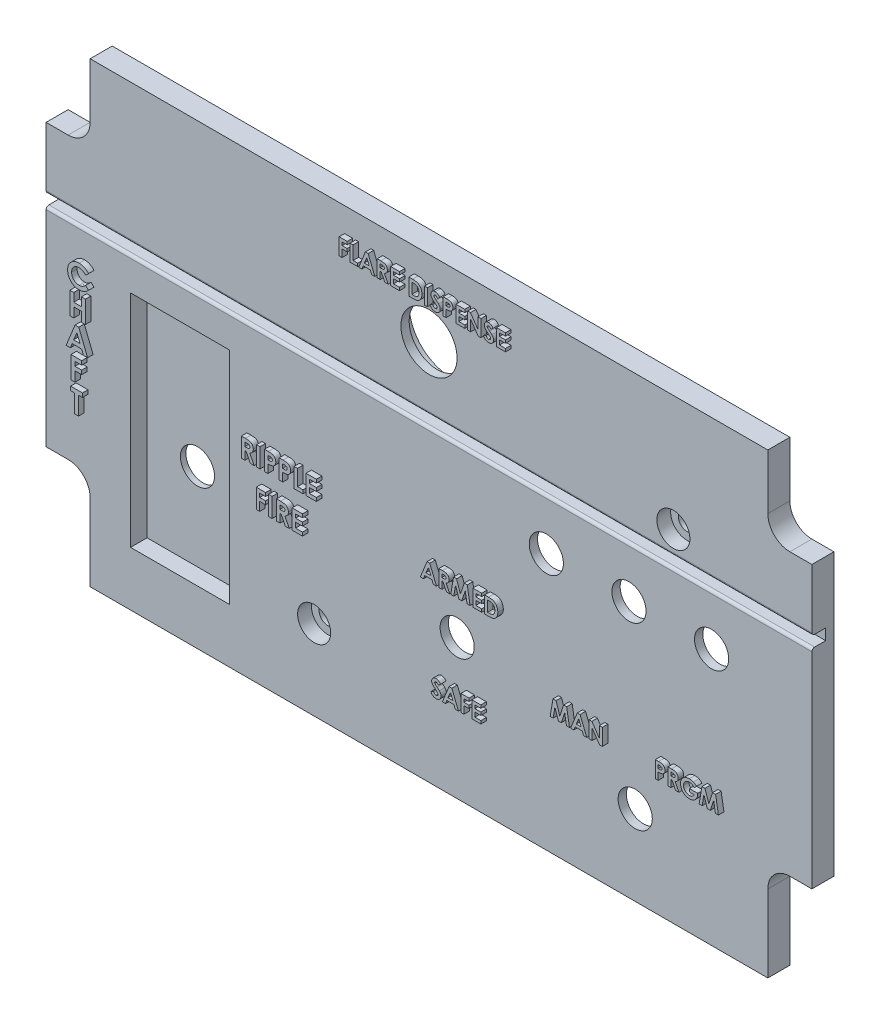
SolidWorks part; units mm, degrees
ref_plane "Front Plane" through (0, 0, 0) normal (0, 0, 1) x (1, 0, 0)
ref_plane "Top Plane" through (0, 0, 0) normal (0, 1, 0) x (1, 0, 0)
ref_plane "Right Plane" through (0, 0, 0) normal (1, 0, 0) x (0, 0, -1)
sketch "Sketch1" plane through (0, 0, 0) normal (0, 0, 1) x (1, 0, 0)
  line L1 (8, 6.6454) -> (131, 6.6454)
  line L2 (0, 24.6454) -> (0, 75.6454)
  line L3 (8, 89.6454) -> (131, 89.6454)
  line L4 (139, 24.6454) -> (139, 75.6454)
  line L13 (8, 89.6454) -> (8, 79.6454)
  line L14 (4, 75.6454) -> (0, 75.6454)
  line L15 (8, 6.6454) -> (8, 20.6454)
  line L16 (4, 24.6454) -> (0, 24.6454)
  line L17 (131, 89.6454) -> (131, 79.6454)
  line L18 (135, 75.6454) -> (139, 75.6454)
  line L19 (131, 6.6454) -> (131, 20.6454)
  line L20 (135, 24.6454) -> (139, 24.6454)
  line L23 (0, 0) -> (0, 87.0008) construction
  arc A8 (8, 20.6454) -> (4, 24.6454) centre (4, 20.6454) ccw
  arc A9 (8, 79.6454) -> (4, 75.6454) centre (4, 79.6454) cw
  arc A11 (131, 20.6454) -> (135, 24.6454) centre (135, 20.6454) cw
  arc A12 (131, 79.6454) -> (135, 75.6454) centre (135, 79.6454) ccw
  circle A14 centre (48.6544, 21.1904) radius 1.6 construction
  circle A15 centre (48.6544, 21.1904) radius 1.6
  circle A16 centre (90.8006, 53.2423) radius 3.1 construction
  circle A17 centre (105.8006, 53.2423) radius 3.1 construction
  circle A18 centre (120.8006, 53.2423) radius 3.1 construction
  circle A19 centre (90.8006, 53.2423) radius 3.1
  circle A35 centre (105.8006, 53.2423) radius 3.1
  circle A37 centre (120.8006, 53.2423) radius 3.1
  circle A47 centre (69.5, 75.8772) radius 5.1 construction
  circle A48 centre (106.9326, 21.1904) radius 3.1 construction
  circle A49 centre (74.6156, 32.0065) radius 3.1 construction
  circle A50 centre (24.475, 32.312) radius 3.1 construction
  circle A51 centre (69.5, 75.8772) radius 5.1
  circle A52 centre (106.9326, 21.1904) radius 3.1
  circle A53 centre (74.6156, 32.0065) radius 3.1
  circle A54 centre (24.475, 32.312) radius 3.1
  circle A55 centre (113.8581, 68.5981) radius 1.6 construction
  circle A56 centre (113.8581, 68.5981) radius 1.6
  point P21 (131, 24.6454)
  point P25 (8, 75.6454)
  point P40 (131, 75.6454)
  dimension "D3" = 18
  dimension "D4" = 14
  dimension "D5" = 8
  dimension "D7" = 83
  dimension "D11" = 8
  dimension "D16" = 139
  dimension "D22" = 8
  dimension "D9" = 8
extrude "Boss-Extrude1" add sketch "Sketch1" along normal blind 4
sketch "Sketch4" plane through (0, 0, 4) normal (0, 0, 1) x (1, 0, 0)
  line L0 (8, 54.5551) -> (8, 14.5758) construction
  line L1 (8, 89.6454) -> (8, 79.6454) construction
  line L2 (-3.2263, 38.4147) -> (14.9404, 38.4147) construction
  line L3 (-3.2263, 33.4147) -> (15.4271, 33.4147) construction
  line L4 (-2.9665, 53.4147) -> (15.2002, 53.4147) construction
  line L5 (-2.9665, 48.4147) -> (15.2002, 48.4147) construction
  line L6 (-2.9665, 43.4147) -> (15.2002, 43.4147) construction
  line L7 (5, 54.5551) -> (5, 14.5758) construction
  text T0 "<b>C</b>" font "Century Gothic" height 4
  text T1 "<b>T</b>" font "Century Gothic" height 4
  text T2 "<b>RIPPLE</b>\r\n<b>  FIRE</b>" font "Century Gothic" height 3.5
  text T5 "<b>F</b>" font "Century Gothic" height 4
  text T7 "<b>FLARE DISPENSE</b>" font "Century Gothic" height 3
  text T9 "<b>H</b>" font "Century Gothic" height 4
  text T10 "<b>A</b>" font "Century Gothic" height 4
  text T11 "<b>ARMED</b>" font "Century Gothic" height 3
  text T12 "<b>SAFE</b>" font "Century Gothic" height 3
  text T13 "<b>MAN</b>" font "Century Gothic" height 3
  text T15 "<b>PRGM</b>" font "Century Gothic" height 3
  dimension "D1" = 3
  dimension "D2" = 5
  dimension "D3" = 5
  dimension "D4" = 5
  dimension "D5" = 5
extrude "Textos" add sketch "Sketch4" along normal blind 1
sketch "Sketch8" plane through (0, 0, 4) normal (0, 0, 1) x (1, 0, 0)
  line L2 (33.3358, 56.5063) -> (15.3354, 56.5063)
  line L3 (33.3358, 56.5063) -> (33.3358, 16.5063)
  line L4 (33.3358, 16.5063) -> (15.3354, 16.5063)
  line L5 (15.3354, 56.5063) -> (15.3354, 16.5063)
  dimension "D1" = 40
  dimension "D2" = 18.0004
extrude "Cut-Extrude3" cut sketch "Sketch8" against normal blind 3
sketch "Sketch9" plane through (0, 0, 4) normal (0, 0, 1) x (1, 0, 0)
  line L0 (0, 75.6454) -> (0, 24.6454) construction
  line L1 (0, 64.4226) -> (139, 64.4226)
  line L2 (0, 64.4226) -> (0, 62.4226)
  line L3 (0, 62.4226) -> (139, 62.4226)
  line L4 (139, 64.4226) -> (139, 62.4226)
  line L5 (139, 24.6454) -> (139, 75.6454) construction
  dimension "D1" = 2
extrude "Cut-Extrude4" cut sketch "Sketch9" against normal blind 2.5
fillet "Fillet1" radius 0.5 2 edges at (69.5, 62.4226, 4) (69.5, 64.4226, 4)
sketch "Sketch10" plane through (0, 0, 4) normal (0, 0, 1) x (1, 0, 0)
  circle A0 centre (48.6544, 21.1904) radius 3
  circle A1 centre (113.8581, 68.5981) radius 3
  dimension "D1" = 6
extrude "Cut-Extrude5" cut sketch "Sketch10" against normal blind 2.5
sketch "Sketch11" plane through (0, 0, 0) normal (0, 0, -1) x (-1, 0, 0)
  circle A0 centre (-69.5, 75.8772) radius 7.6
  circle A1 centre (-90.8006, 53.2423) radius 6.7
  circle A2 centre (-105.8006, 53.2423) radius 6.7
  circle A3 centre (-120.8006, 53.2423) radius 6.7
  circle A5 centre (-74.6156, 32.0065) radius 6.7
  circle A6 centre (-106.9326, 21.1904) radius 6.7
  dimension "D1" = 15.2
  dimension "D2" = 13.4
extrude "Back holes" cut sketch "Sketch11" against normal blind 2.5
